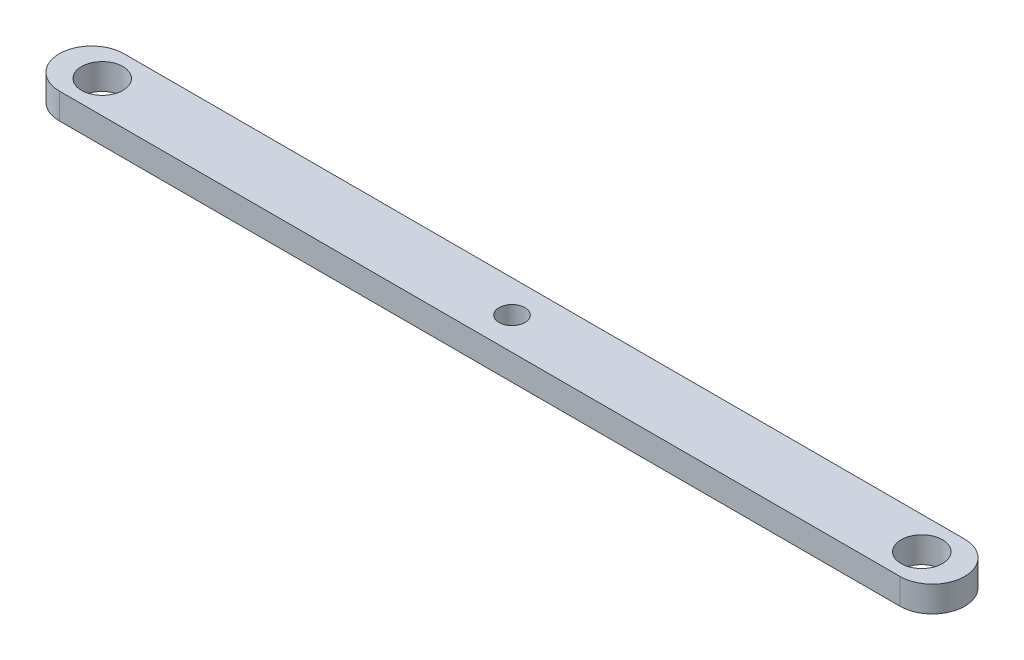
SolidWorks part; units mm, degrees
ref_plane "Front Plane" through (0, 0, 0) normal (0, 0, 1) x (1, 0, 0)
ref_plane "Top Plane" through (0, 0, 0) normal (0, 1, 0) x (1, 0, 0)
ref_plane "Right Plane" through (0, 0, 0) normal (1, 0, 0) x (0, 0, -1)
sketch "Sketch1" plane through (0, 0, 0) normal (0, 1, 0) x (1, 0, 0)
  line L1 (0, 0) -> (70, 0)
  line L2 (0, 0) -> (0, 5)
  line L3 (0, 5) -> (70, 5)
  line L4 (70, 0) -> (70, 5)
  dimension "D1" = 70
  dimension "D2" = 5
extrude "Boss-Extrude1" add sketch "Sketch1" along normal blind 2
sketch "Sketch2" plane through (0, 2, 0) normal (0, 1, 0) x (1, 0, 0)
  line L0 (0, 2.5) -> (70, 2.5) construction
  line L1 (0, 5) -> (0, 0) construction
  line L2 (70, 0) -> (70, 5) construction
  line L3 (35, 0) -> (35, 5) construction
  line L4 (0, 0) -> (70, 0) construction
  line L5 (70, 5) -> (0, 5) construction
  circle A0 centre (66.6829, 2.5) radius 1.6
  circle A1 centre (3.3171, 2.5) radius 1.6
  dimension "D1" = 63.3658
  dimension "D2" = 3.2
extrude "Cut-Extrude1" cut sketch "Sketch2" against normal through all and the other way through all
sketch "Sketch4" plane through (0, 2, 0) normal (0, 1, 0) x (1, 0, 0)
  line L0 (70, 5) -> (0, 5) construction
  line L3 (32.5, 5) -> (37.5, 5)
  line L5 (35, 5) -> (35, 0) construction
  line L6 (0, 0) -> (70, 0) construction
  circle A0 centre (35, 2.5) radius 1
  point P8 (35, 5)
  dimension "D2" = 2
  dimension "D1" = 5
extrude "Cut-Extrude2" cut sketch "Sketch4" against normal up to next contours A0
fillet "Fillet2" 2 edges at (0, 1, 0) (0, 1, -5) type full round first side face at (35, 1, 0) second side face at (35, 1, -5) middle face at (0, 1, -2.5)
fillet "Fillet3" 2 edges at (70, 1, -5) (70, 1, 0) type full round first side face at (36.25, 1, -5) second side face at (36.25, 1, 0) middle face at (70, 1, -2.5)
